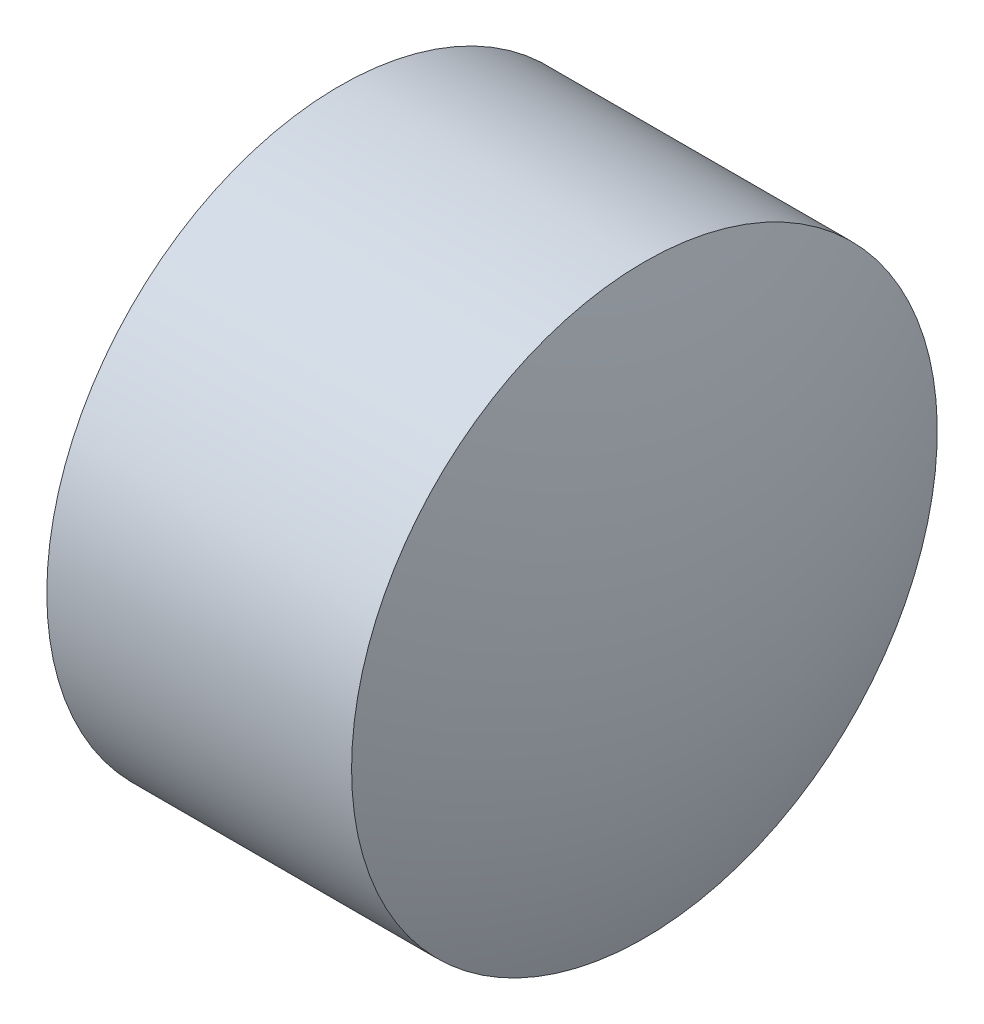
SolidWorks part; units mm, degrees
ref_plane "Front Plane" through (0, 0, 0) normal (0, 0, 1) x (1, 0, 0)
ref_plane "Top Plane" through (0, 0, 0) normal (0, 1, 0) x (1, 0, 0)
ref_plane "Right Plane" through (0, 0, 0) normal (1, 0, 0) x (0, 0, -1)
sketch "BodySke" plane through (0, 0, 0) normal (0, 0, 1) x (1, 0, 0)
  line L0 (0, 0) -> (3.28, 0) construction
  line L1 (2, 0) -> (2, 1.5) construction
  line L2 (1.723, 1.5) -> (1.723, 0) construction
  line L3 (2, 1.5) -> (0, 1.5) construction
  line L4 (0, 1.5) -> (0, 0)
  line L5 (0, 0) -> (2, 0)
  line L6 (1.5, 3.0647) -> (1.5, -0.3929) construction
  line L7 (0, 1.5) -> (1.723, 1.5)
  arc A0 (2, 0) -> (1.723, 1.5) centre (-2.2, 0) ccw
  point P5 (0, 1.2195)
  dimension "Oval_Radius" = 4.2
  dimension "Minor_dia" = 2.439
  dimension "Diameter" = 3
  dimension "Advance" = 0.5
revolve "BaseBody" add sketch "BodySke" angle 360 about L0
cosmetic thread "ThreadCosmetic" [suppressed] parameters "Minor_dia"=2.439
sketch "HeadChamferSke" plane through (0, 0, 0) normal (0, 0, 1) x (1, 0, 0)
  line L0 (0, 0) -> (2.4505, 0) construction
  line L1 (0, 1.5) -> (0, 1.2195)
  line L2 (0, 1.5) -> (0.1619, 1.5)
  line L3 (0.1619, 1.5) -> (0, 1.2195)
  line L6 (0, 1.5) -> (0, 0) construction
  line L7 (1.723, 1.5) -> (0, 1.5) construction
  dimension "Angle" = 30
revolve "HeadChamfer" cut sketch "HeadChamferSke" angle 360 about L0
sketch "HexagonSocketSke" plane through (0, 0, 0) normal (-1, 0, 0) x (0, 0, 1)
  line L1 (0, 0.866) -> (-0.75, 0.433)
  line L2 (-0.75, 0.433) -> (-0.75, -0.433)
  line L3 (-0.75, -0.433) -> (0, -0.866)
  line L4 (0, -0.866) -> (0.75, -0.433)
  line L5 (0.75, -0.433) -> (0.75, 0.433)
  line L6 (0.75, 0.433) -> (0, 0.866)
  circle A0 centre (0, 0) radius 0.75 construction
  dimension "Hexagon_Width" = 1.5
extrude "HexagonSocket" cut sketch "HexagonSocketSke" against normal blind 1.2
sketch "ThdSchSke" plane through (0, 0, 0) normal (0, 0, 1) x (1, 0, 0)
  line L0 (0, 0) -> (2.6881, 0) construction
  line L1 (0.3381, 1.8239) -> (0.3381, 1.5)
  line L2 (0.3381, 1.8239) -> (0.6619, 1.8239)
  line L3 (0.6619, 1.8239) -> (0.6619, 1.5)
  line L4 (0.6619, 1.5) -> (0.5, 1.2195)
  line L5 (0.5, 1.2195) -> (0.3381, 1.5)
  line L7 (0, 1.5) -> (1.723, 1.5) construction
  dimension "D1" = 0.5
revolve "ThreadSchematic" [suppressed] cut sketch "ThdSchSke" angle 360 about L0
pattern_linear "ThdSchPat" [suppressed] count 3 along (1, 0, 0) of bodies 104
equation "\"Minor_dia@ThreadCosmetic\" = \"Minor_dia@BodySke\""
equation "\"D1@ThdSchSke\" = \"Advance@BodySke\""
equation "\"Advance@ThdSchPat\" = \"Advance@BodySke\""
equation "\"D1@ThdSchPat\" =  int(\"Length@BodySke\" / \"Advance@BodySke\"  )  - 1"
